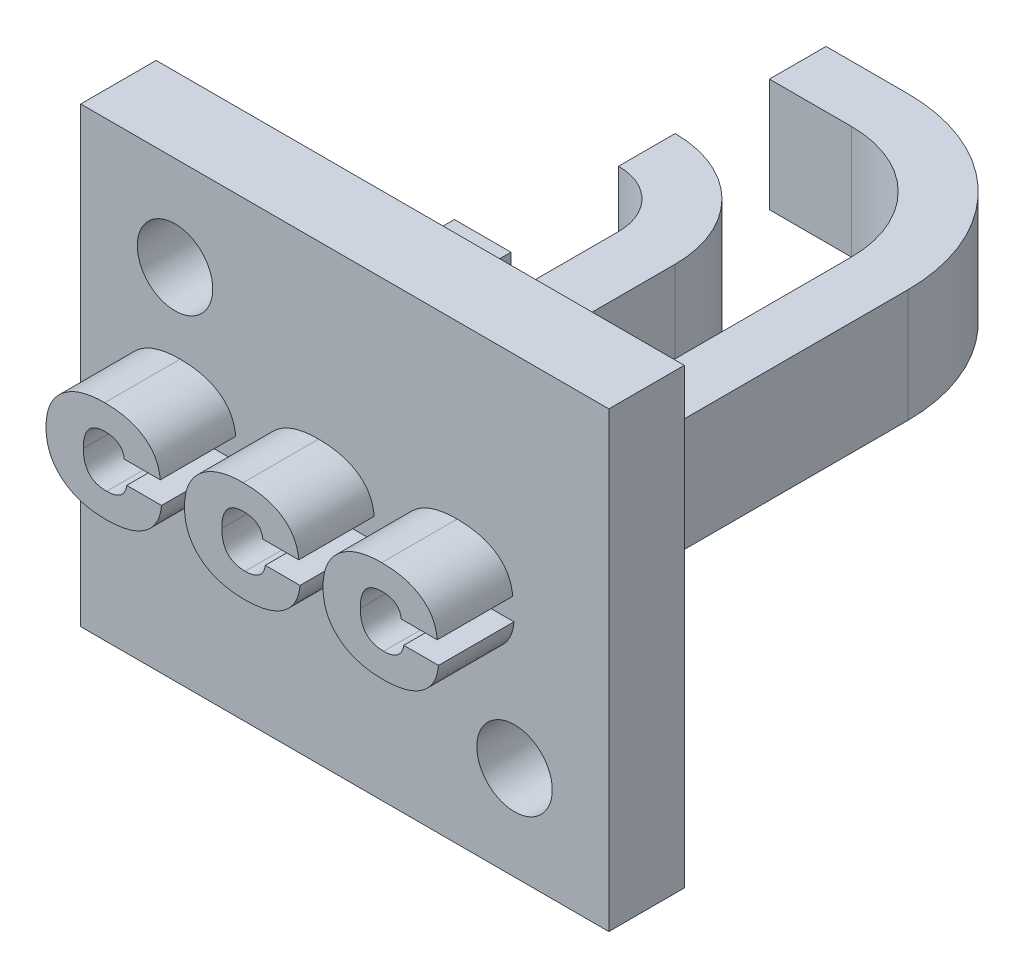
SolidWorks part; units mm, degrees
ref_plane "Front Plane" through (0, 0, 0) normal (0, 0, 1) x (1, 0, 0)
ref_plane "Top Plane" through (0, 0, 0) normal (0, 1, 0) x (1, 0, 0)
ref_plane "Right Plane" through (0, 0, 0) normal (1, 0, 0) x (0, 0, -1)
sketch "Sketch1" plane through (0, 0, 0) normal (0, 0, 1) x (1, 0, 0)
  line L1 (-7.5, 6) -> (7.5, 6)
  line L2 (-7.5, 6) -> (-7.5, -6)
  line L3 (-7.5, -6) -> (7.5, -6)
  line L4 (7.5, 6) -> (7.5, -6)
  line L5 (-7.5, 6) -> (7.5, -6) construction
  line L6 (-7.5, -6) -> (7.5, 6) construction
  point P0 (0, 0)
  dimension "D1" = 15
  dimension "D2" = 12
extrude "Boss-Extrude1" add sketch "Sketch1" along normal blind 2
sketch "Sketch2" plane through (0, 0, 2) normal (0, 0, 1) x (1, 0, 0)
  text T0 "CCC" font "Swis721 Blk BT" height in points 10
  dimension "D1" = 6.585
extrude "Boss-Extrude2" add sketch "Sketch2" along normal blind 2
sketch "Sketch3" plane through (0, 0, 0) normal (0, 1, 0) x (1, 0, 0)
  line L0 (7.5, 0) -> (-7.5, 0) construction
  line L1 (1.7287, 0) -> (3.2287, 0)
  line L2 (1.7287, 0) -> (1.7287, 12.2)
  line L3 (-3.644, -2) -> (-3.644, 5.3789) construction
  line L4 (3.2287, 0) -> (3.2287, 13.7)
  line L5 (-4.394, 0) -> (-2.894, 0)
  line L6 (-4.394, 0) -> (-4.394, 4.8)
  line L7 (-1.1926, -2) -> (-1.1926, 4.6797) construction
  line L8 (-2.894, 0) -> (-2.894, 4.8)
  line L9 (-2.894, 4.8) -> (-4.394, 4.8)
  line L10 (-1.9426, 0) -> (-0.4426, 0)
  line L13 (-1.9426, 0) -> (-1.9426, 8.2)
  line L14 (2.4787, -2) -> (2.4787, 2.787) construction
  line L15 (-0.4426, 0) -> (-0.4426, 9.7)
  line L16 (-0.4426, 9.7) -> (-3.4426, 9.7)
  line L17 (-3.4426, 13.7) -> (3.2287, 13.7)
  line L18 (-1.9426, 8.2) -> (-3.4426, 8.2)
  line L19 (-3.4426, 9.7) -> (-3.4426, 8.2)
  line L20 (-3.4426, 13.7) -> (-3.4426, 12.2)
  line L21 (-3.4426, 12.2) -> (1.7287, 12.2)
  dimension "D1" = 1.5
  dimension "D2" = 4.8
  dimension "D3" = 1.5
  dimension "D4" = 1.5
  dimension "D5" = 8.2
  dimension "D6" = 1.5
  dimension "D7" = 2.5
  dimension "D8" = 1.5
  dimension "D9" = 1.5
  dimension "D10" = 3.644
extrude "Boss-Extrude3" add sketch "Sketch3" along normal mid plane 3
fillet "Fillet3" radius 1.5 1 edges at (-1.9426, 0, -8.2)
fillet "Fillet4" radius 3 1 edges at (-0.4426, 0, -9.7)
fillet "Fillet5" radius 3 1 edges at (1.7287, 0, -12.2)
fillet "Fillet6" radius 4.5 1 edges at (3.2287, 0, -13.7)
sketch "Sketch4" plane through (7.5, 0, 0) normal (1, 0, 0) x (0, 0, -1)
  line L4 (0, -6) -> (0, 6)
  line L5 (0, 6) -> (-2, 6)
  line L6 (-2, 6) -> (-2, -6)
  line L7 (-2, -6) -> (0, -6)
  line L8 (0, -6) -> (0, 6)
  line L9 (0, 6) -> (-2, 6)
  line L10 (-2, 6) -> (-2, -6)
  line L11 (-2, -6) -> (0, -6)
  dimension "D1" = 0
extrude "Cut-Extrude1" cut sketch "Sketch4" against normal blind 1
sketch "Sketch5" plane through (0, 0, 0) normal (0, 0, -1) x (-1, 0, 0)
  line L0 (-6.5, -6) -> (-6.5, 6) construction
  line L1 (7.5, -6) -> (-6.5, -6) construction
  line L2 (7.5, 6) -> (7.5, -6) construction
  line L3 (-6.5, 6) -> (7.5, 6) construction
  circle A0 centre (-4, -3.5) radius 1
  circle A1 centre (5, 3.5) radius 1
  dimension "D1" = 2
  dimension "D2" = 2.5
  dimension "D3" = 2.5
  dimension "D4" = 2.5
  dimension "D5" = 2.5
extrude "Cut-Extrude2" cut sketch "Sketch5" against normal through all
